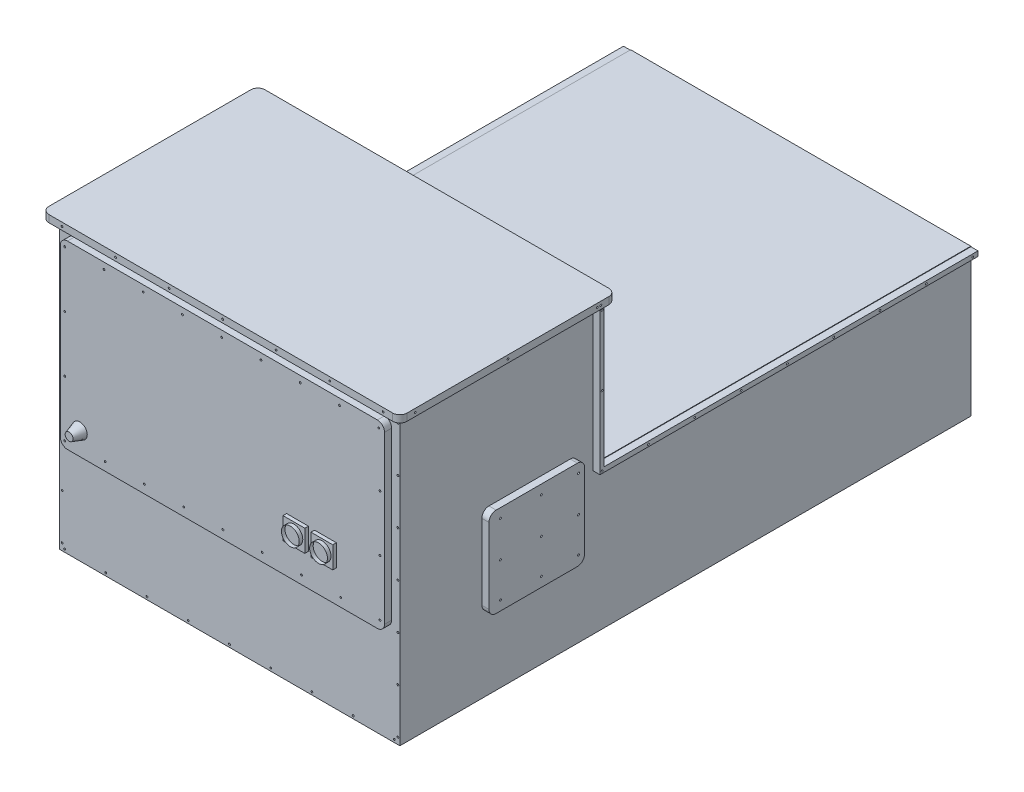
SolidWorks part; units mm, degrees
ref_plane "Front Plane" through (0, 0, 0) normal (0, 0, 1) x (1, 0, 0)
ref_plane "Top Plane" through (0, 0, 0) normal (0, 1, 0) x (1, 0, 0)
ref_plane "Right Plane" through (0, 0, 0) normal (1, 0, 0) x (0, 0, -1)
sketch "Sketch1" plane through (0, 0, 0) normal (0, 0, 1) x (1, 0, 0)
  line L1 (47.6701, -20.6273) -> (-47.6701, -20.6273)
  line L2 (47.6701, -20.6273) -> (47.6701, 20.6273)
  line L3 (47.6701, 20.6273) -> (-47.6701, 20.6273)
  line L4 (-47.6701, -20.6273) -> (-47.6701, 20.6273)
  line L5 (47.6701, -20.6273) -> (-47.6701, 20.6273) construction
  line L6 (47.6701, 20.6273) -> (-47.6701, -20.6273) construction
  point P0 (0, 0)
extrude "Boss-Extrude1" add sketch "Sketch1" along normal blind 160
sketch "Sketch2" plane through (0, 20.6273, 0) normal (0, 1, 0) x (1, 0, 0)
  line L0 (47.6701, -160) -> (47.6701, 0) construction
  line L1 (-47.6701, -160) -> (47.6701, -160)
  line L2 (-47.6701, -160) -> (-47.6701, -104.4412)
  line L3 (-47.6701, -104.4412) -> (47.6701, -104.4412)
  line L4 (47.6701, -160) -> (47.6701, -104.4412)
extrude "Boss-Extrude2" add sketch "Sketch2" along normal blind 40
sketch "Sketch3" plane through (-47.6701, 0, 0) normal (-1, 0, 0) x (0, 0, 1)
  line L0 (104.4412, 20.6273) -> (104.4412, 19.1273)
  line L1 (0, 20.6273) -> (104.4412, 20.6273)
  line L2 (0, 20.6273) -> (0, 19.1273)
  line L3 (0, 19.1273) -> (105.9412, 19.1273)
  line L5 (104.4412, 60.6273) -> (105.9412, 60.6273)
  line L6 (104.4412, 60.6273) -> (104.4412, 20.6273)
  line L7 (104.4412, 19.1273) -> (105.9412, 19.1273)
  line L8 (105.9412, 60.6273) -> (105.9412, 19.1273)
  line L9 (104.4412, 19.1273) -> (0, 19.1273)
  line L10 (112.2516, 25.0918) -> (135.0314, 25.0918)
  line L11 (110.2516, 23.0918) -> (110.2516, 2)
  line L12 (112.2516, 0) -> (135.0314, 0)
  line L13 (137.0314, 23.0918) -> (137.0314, 2)
  line L14 (0, 20.4879) -> (104.7525, 20.4879)
  line L15 (104.7525, 20.4879) -> (104.7525, 60.6273)
  arc A0 (135.0314, 0) -> (137.0314, 2) centre (135.0314, 2) ccw
  arc A1 (112.2516, 0) -> (110.2516, 2) centre (112.2516, 2) cw
  arc A2 (112.2516, 25.0918) -> (110.2516, 23.0918) centre (112.2516, 23.0918) ccw
  arc A3 (137.0314, 23.0918) -> (135.0314, 25.0918) centre (135.0314, 23.0918) ccw
  line M16 (160, 60.6273) -> (104.4412, 60.6273)
  dimension "D3" = 2
  dimension "D1" = 1.5
  dimension "D2" = 1.5
extrude "Boss-Extrude3" add sketch "Sketch3" along normal blind 2 contours L14 L2 L3 L0 | L15 L14 L0 L3 L8 M16 | L13 A3 L10 A2 L11 A1 L12 A0 region at (-47.6701, 39.7065, 105.3405) region at (-47.6701, 19.8076, 52.2206) region at (-47.6701, 12.5459, 123.6415)
hole_wizard "#0-80 Tapped Hole1" positions "3DSketch12" profile "Sketch8" tap size "#0-80" standard "ANSI Inch"
sketch3d "3DSketch12"
  point P0 (-49.6701, 19.7426, 1.488)
sketch "Sketch8" plane through (-49.6701, 19.7426, 1.488) normal (0, 1, 0) x (0, 0, 1)
  line L0 (0, 0) -> (0, 16.8326)
  line L1 (0, 16.8326) -> (0.254, 16.68)
  line L2 (0.254, 16.68) -> (0.254, 0)
  line L5 (0.254, 0) -> (0, 0)
  line L10 (0, 16.8326) -> (-0.254, 16.68) construction
  line L11 (0, -6.35) -> (0, 107.95) construction
  dimension "Tap Drill Dia." = 0.508
  dimension "Tap Drill Depth" = 16.68
  dimension "Drill Angle" = 118
pattern_linear "LPattern1" count 3 spacing 19.5 along (0, 1, 0) count 10 spacing 12.98 along (0, 0, 1) skipping (0, 9), (1, 0), (1, 1), (1, 2), (1, 3), (1, 4), (1, 5), (1, 6), (1, 7), (1, 9), (2, 0), (2, 1), (2, 2), (2, 3), (2, 4), (2, 5), (2, 6), (2, 7), (2, 9) of "#0-80 Tapped Hole1"
hole_wizard "#0-80 Tapped Hole3" positions "Sketch11" profile "Sketch12" tap size "#0-80" standard "ANSI Inch"
sketch "Sketch11" plane through (-49.6701, 0, 0) normal (-1, 0, 0) x (0, 0, 1)
  point P0 (111.9351, 22.4763)
  point P2 (111.9351, 2.6662)
  point P4 (122.3524, 2.6662)
  point P6 (133.7944, 2.6662)
  point P8 (133.7944, 12.4005)
  point P10 (133.7944, 22.4763)
  point P12 (122.3524, 12.4005)
  point P14 (111.9351, 12.4005)
  point P16 (122.3524, 22.4763)
sketch "Sketch12" plane through (-49.6701, 22.4763, 111.9351) normal (0, 1, 0) x (0, 0, 1)
  line L0 (0, 0) -> (0, 16.8326)
  line L1 (0, 16.8326) -> (0.254, 16.68)
  line L2 (0.254, 16.68) -> (0.254, 0)
  line L5 (0.254, 0) -> (0, 0)
  line L10 (0, 16.8326) -> (-0.254, 16.68) construction
  line L11 (0, -6.35) -> (0, 107.95) construction
  dimension "Tap Drill Dia." = 0.508
  dimension "Tap Drill Depth" = 16.68
  dimension "Drill Angle" = 118
sketch "Sketch13" plane through (0, 60.6273, 0) normal (0, 1, 0) x (1, 0, 0)
  line L0 (47.6701, -160) -> (47.6701, -104.4412) construction
  line L5 (-47.6701, -105.9412) -> (-47.6701, -160) construction
  line L6 (-48.1701, -101.9412) -> (48.1701, -101.9412)
  line L8 (47.6701, -104.4412) -> (-47.6701, -104.4412) construction
  line L9 (-47.6701, -160) -> (47.6701, -160) construction
  line L11 (-50.1701, -103.9412) -> (-50.1701, -160.5)
  line L12 (-48.1701, -162.5) -> (48.1701, -162.5)
  line L13 (50.1701, -103.9412) -> (50.1701, -160.5)
  arc A0 (50.1701, -160.5) -> (48.1701, -162.5) centre (48.1701, -160.5) cw
  arc A1 (50.1701, -103.9412) -> (48.1701, -101.9412) centre (48.1701, -103.9412) ccw
  arc A2 (-48.1701, -101.9412) -> (-50.1701, -103.9412) centre (-48.1701, -103.9412) ccw
  arc A3 (-48.1701, -162.5) -> (-50.1701, -160.5) centre (-48.1701, -160.5) cw
  point P7 (0, -101.9412)
  point P12 (0, -104.4412)
  point P13 (0, -162.5)
  point P16 (0, -160)
  dimension "D5" = 2
  dimension "D1" = 2.5
  dimension "D2" = 2.5
  dimension "D3" = 2.5
  dimension "D4" = 2.5
extrude "Boss-Extrude4" add sketch "Sketch13" along normal blind 1 and the other way blind 1
hole_wizard "#0-80 Tapped Hole4" positions "3DSketch13" profile "Sketch18" tap size "#0-80" standard "ANSI Inch"
sketch3d "3DSketch13"
  point P0 (-50.1701, 60.5924, 107.2061)
sketch "Sketch18" plane through (-50.1701, 60.5924, 107.2061) normal (0, 1, 0) x (0, 0, 1)
  line L0 (0, 0) -> (0, 16.8326)
  line L1 (0, 16.8326) -> (0.254, 16.68)
  line L2 (0.254, 16.68) -> (0.254, 0)
  line L5 (0.254, 0) -> (0, 0)
  line L10 (0, 16.8326) -> (-0.254, 16.68) construction
  line L11 (0, -6.35) -> (0, 107.95) construction
  dimension "Tap Drill Dia." = 0.508
  dimension "Tap Drill Depth" = 16.68
  dimension "Drill Angle" = 118
pattern_linear "LPattern2" count 3 spacing 26 along (0, 0, 1) of "#0-80 Tapped Hole4"
hole_wizard "#0-80 Tapped Hole5" positions "3DSketch14" profile "Sketch19" tap size "#0-80" standard "ANSI Inch"
sketch3d "3DSketch14"
  point P0 (-44.5084, 60.5755, 162.5)
sketch "Sketch19" plane through (-44.5084, 60.5755, 162.5) normal (1, 0, 0) x (0, -1, 0)
  line L0 (0, 0) -> (0, 16.8326)
  line L1 (0, 16.8326) -> (0.254, 16.68)
  line L2 (0.254, 16.68) -> (0.254, 0)
  line L5 (0.254, 0) -> (0, 0)
  line L10 (0, 16.8326) -> (-0.254, 16.68) construction
  line L11 (0, -6.35) -> (0, 107.95) construction
  dimension "Tap Drill Dia." = 0.508
  dimension "Tap Drill Depth" = 16.68
  dimension "Drill Angle" = 118
pattern_linear "LPattern3" count 7 spacing 15 along (1, 0, 0) of "#0-80 Tapped Hole5"
hole_wizard "#0-80 Tapped Hole7" positions "3DSketch16" profile "Sketch21" tap size "#0-80" standard "ANSI Inch"
sketch3d "3DSketch16"
  point P0 (-46.2777, -19.8551, 160)
sketch "Sketch21" plane through (-46.2777, -19.8551, 160) normal (1, 0, 0) x (0, -1, 0)
  line L0 (0, 0) -> (0, 16.8326)
  line L1 (0, 16.8326) -> (0.254, 16.68)
  line L2 (0.254, 16.68) -> (0.254, 0)
  line L5 (0.254, 0) -> (0, 0)
  line L10 (0, 16.8326) -> (-0.254, 16.68) construction
  line L11 (0, -6.35) -> (0, 107.95) construction
  dimension "Tap Drill Dia." = 0.508
  dimension "Tap Drill Depth" = 16.68
  dimension "Drill Angle" = 118
pattern_linear "LPattern5" count 9 spacing 11.55 along (1, 0, 0) of "#0-80 Tapped Hole7"
hole_wizard "#0-80 Tapped Hole8" positions "3DSketch18" profile "Sketch23" tap size "#0-80" standard "ANSI Inch"
sketch3d "3DSketch18"
  point P0 (-46.9525, -18.6665, 160)
sketch "Sketch23" plane through (-46.9525, -18.6665, 160) normal (1, 0, 0) x (0, -1, 0)
  line L0 (0, 0) -> (0, 16.8326)
  line L1 (0, 16.8326) -> (0.254, 16.68)
  line L2 (0.254, 16.68) -> (0.254, 0)
  line L5 (0.254, 0) -> (0, 0)
  line L10 (0, 16.8326) -> (-0.254, 16.68) construction
  line L11 (0, -6.35) -> (0, 107.95) construction
  dimension "Tap Drill Dia." = 0.508
  dimension "Tap Drill Depth" = 16.68
  dimension "Drill Angle" = 118
pattern_linear "LPattern6" count 7 spacing 12.7 along (0, 1, 0) of "#0-80 Tapped Hole8"
hole_wizard "#0-80 Tapped Hole9" positions "3DSketch19" profile "Sketch24" tap size "#0-80" standard "ANSI Inch"
sketch3d "3DSketch19"
  point P0 (47.112, -18.8058, 160)
sketch "Sketch24" plane through (47.112, -18.8058, 160) normal (1, 0, 0) x (0, -1, 0)
  line L0 (0, 0) -> (0, 16.8326)
  line L1 (0, 16.8326) -> (0.254, 16.68)
  line L2 (0.254, 16.68) -> (0.254, 0)
  line L5 (0.254, 0) -> (0, 0)
  line L10 (0, 16.8326) -> (-0.254, 16.68) construction
  line L11 (0, -6.35) -> (0, 107.95) construction
  dimension "Tap Drill Dia." = 0.508
  dimension "Tap Drill Depth" = 16.68
  dimension "Drill Angle" = 118
pattern_linear "LPattern7" count 7 spacing 12.7 along (0, 1, 0) of "#0-80 Tapped Hole9"
sketch "Sketch25" plane through (0, 0, 160) normal (0, 0, 1) x (1, 0, 0)
  line L1 (-43.4714, 57.3024) -> (43.3623, 57.3024)
  line L2 (-45.4714, 55.3024) -> (-45.4714, 8.7059)
  line L3 (-43.4714, 6.7059) -> (43.3623, 6.7059)
  line L4 (45.3623, 55.3024) -> (45.3623, 8.7059)
  arc A0 (45.3623, 55.3024) -> (43.3623, 57.3024) centre (43.3623, 55.3024) ccw
  arc A1 (45.3623, 8.7059) -> (43.3623, 6.7059) centre (43.3623, 8.7059) cw
  arc A2 (-43.4714, 6.7059) -> (-45.4714, 8.7059) centre (-43.4714, 8.7059) cw
  arc A3 (-43.4714, 57.3024) -> (-45.4714, 55.3024) centre (-43.4714, 55.3024) ccw
  dimension "D1" = 2
extrude "Boss-Extrude5" add sketch "Sketch25" along normal blind 2
hole_wizard "#0-80 Tapped Hole10" positions "3DSketch20" profile "Sketch26" tap size "#0-80" standard "ANSI Inch"
sketch3d "3DSketch20"
  point P0 (-44.2601, 55.5251, 162)
sketch "Sketch26" plane through (-44.2601, 55.5251, 162) normal (1, 0, 0) x (0, -1, 0)
  line L0 (0, 0) -> (0, 16.8326)
  line L1 (0, 16.8326) -> (0.254, 16.68)
  line L2 (0.254, 16.68) -> (0.254, 0)
  line L5 (0.254, 0) -> (0, 0)
  line L10 (0, 16.8326) -> (-0.254, 16.68) construction
  line L11 (0, -6.35) -> (0, 107.95) construction
  dimension "Tap Drill Dia." = 0.508
  dimension "Tap Drill Depth" = 16.68
  dimension "Drill Angle" = 118
pattern_linear "LPattern8" count 4 spacing 15.7 along (0, -1, 0) count 9 spacing 11 along (1, 0, 0) of "#0-80 Tapped Hole10" pattern seed only yes
hole_wizard "#0-80 Tapped Hole11" positions "3DSketch24" profile "Sketch30" tap size "#0-80" standard "ANSI Inch"
sketch3d "3DSketch24"
  point P0 (44.0873, 9.052, 162)
sketch "Sketch30" plane through (44.0873, 9.052, 162) normal (1, 0, 0) x (0, -1, 0)
  line L0 (0, 0) -> (0, 16.8326)
  line L1 (0, 16.8326) -> (0.254, 16.68)
  line L2 (0.254, 16.68) -> (0.254, 0)
  line L5 (0.254, 0) -> (0, 0)
  line L10 (0, 16.8326) -> (-0.254, 16.68) construction
  line L11 (0, -6.35) -> (0, 107.95) construction
  dimension "Tap Drill Dia." = 0.508
  dimension "Tap Drill Depth" = 16.68
  dimension "Drill Angle" = 118
pattern_linear "LPattern10" count 3 spacing 15.7 along (0, 1, 0) count 8 spacing 11 along (-1, 0, 0) of "#0-80 Tapped Hole11" pattern seed only yes
hole_wizard "#0-80 Tapped Hole12" positions "3DSketch25" profile "Sketch31" tap size "#0-80" standard "ANSI Inch"
sketch3d "3DSketch25"
  point P0 (50.1701, 60.6067, 158.1847)
sketch "Sketch31" plane through (50.1701, 60.6067, 158.1847) normal (0, 1, 0) x (0, 0, -1)
  line L0 (0, 0) -> (0, 16.8326)
  line L1 (0, 16.8326) -> (0.254, 16.68)
  line L2 (0.254, 16.68) -> (0.254, 0)
  line L5 (0.254, 0) -> (0, 0)
  line L10 (0, 16.8326) -> (-0.254, 16.68) construction
  line L11 (0, -6.35) -> (0, 107.95) construction
  dimension "Tap Drill Dia." = 0.508
  dimension "Tap Drill Depth" = 16.68
  dimension "Drill Angle" = 118
pattern_linear "LPattern11" count 3 spacing 26 along (0, 0, -1) of "#0-80 Tapped Hole12"
mirror "Mirror3" about plane through (0, 0, 0) normal (1, 0, 0) of "LPattern1", "#0-80 Tapped Hole4", "#0-80 Tapped Hole1", "#0-80 Tapped Hole3", "Boss-Extrude3"
sketch "Sketch32" plane through (0, 0, 162) normal (0, 0, 1) x (1, 0, 0)
  circle A0 centre (-40.0146, 13.0506) radius 2.0871
extrude "Boss-Extrude6" add sketch "Sketch32" along normal blind 3 draft 18
sketch "Sketch33" plane through (0, 0, 162) normal (0, 0, 1) x (1, 0, 0)
  line L1 (24.0281, 21.8652) -> (17.9119, 21.8652)
  line L2 (24.0281, 21.8652) -> (24.0281, 15.749)
  line L3 (24.0281, 15.749) -> (17.9119, 15.749)
  line L4 (17.9119, 21.8652) -> (17.9119, 15.749)
  line L5 (24.0281, 21.8652) -> (17.9119, 15.749) construction
  line L6 (24.0281, 15.749) -> (17.9119, 21.8652) construction
  line L7 (25.7437, 21.756) -> (31.8599, 21.756)
  line L8 (25.7437, 21.756) -> (25.7437, 15.6398)
  line L9 (25.7437, 15.6398) -> (31.8599, 15.6398)
  line L10 (31.8599, 21.756) -> (31.8599, 15.6398)
  point P0 (20.97, 18.8071)
extrude "Boss-Extrude7" add sketch "Sketch33" along normal blind 1
sketch "Sketch34" plane through (0, 0, 163) normal (0, 0, 1) x (1, 0, 0)
  circle A0 centre (20.9666, 18.8529) radius 2.4951
  circle A1 centre (28.8727, 18.7366) radius 2.4951
  point P2 (23.5245, 19.8218)
surface "Surface-Extrude1" sketch "Sketch34" parameters "D1"=1
